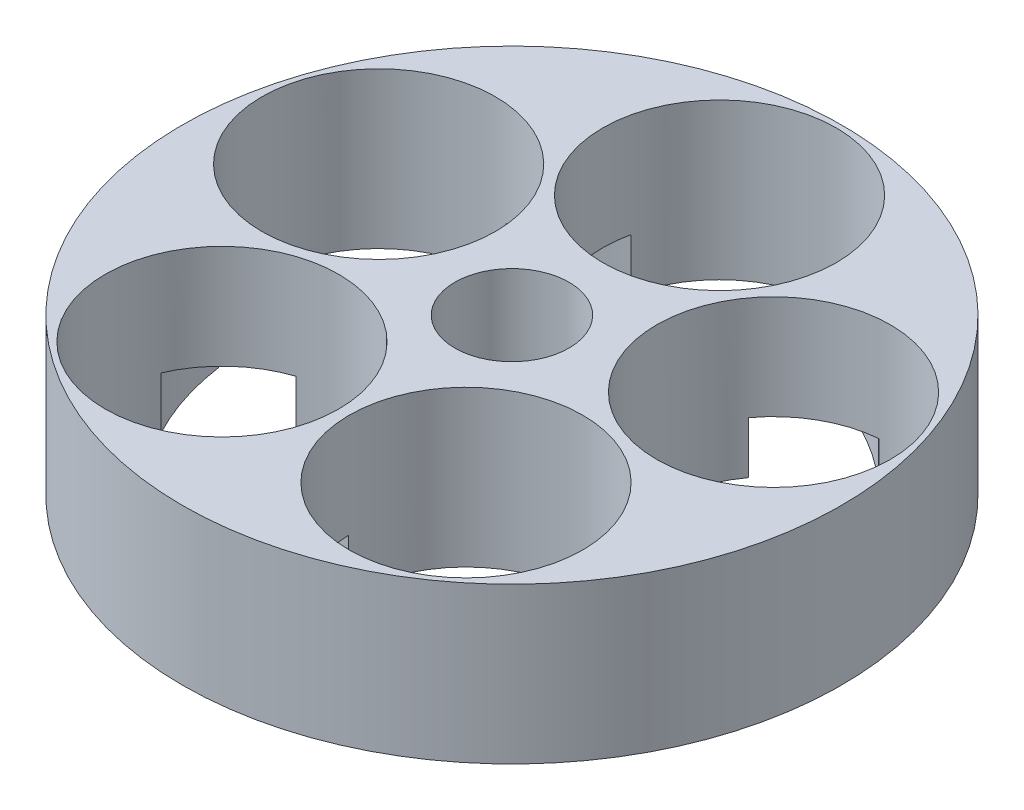
SolidWorks part; units mm, degrees
ref_plane "Front Plane" through (0, 0, 0) normal (0, 0, 1) x (1, 0, 0)
ref_plane "Top Plane" through (0, 0, 0) normal (0, 1, 0) x (1, 0, 0)
ref_plane "Right Plane" through (0, 0, 0) normal (1, 0, 0) x (0, 0, -1)
sketch "Sketch1" plane through (0, 0, 0) normal (0, 1, 0) x (1, 0, 0)
  line L0 (0, -164.5173) -> (0, 163.7587) construction
  line L1 (-104.9541, 34.1017) -> (106.3821, -34.5656) construction
  line L2 (-169.6132, -123.2312) -> (93.1873, 67.7046) construction
  line L3 (-107.5036, 0) -> (118.5963, 0) construction
  line L4 (-102.8693, -33.4243) -> (102.8693, 33.4243) construction
  line L5 (-62.7697, -86.3951) -> (62.7697, 86.3951) construction
  circle A0 centre (0, 0) radius 63.5
  circle A1 centre (38.0423, 12.3607) radius 22.5
  circle A4 centre (0, 40) radius 22.5
  circle A5 centre (-38.0423, 12.3607) radius 22.5
  circle A6 centre (-23.5114, -32.3607) radius 22.5
  circle A10 centre (23.5114, -32.3607) radius 22.5
  circle A11 centre (0, 0) radius 11
  point P15 (0, 0)
  dimension "D1" = 127
  dimension "D4" = 45
  dimension "D5" = 40
  dimension "D7" = 40
  dimension "D8" = 40
  dimension "D9" = 40
  dimension "D10" = 72
  dimension "D12" = 40
  dimension "D14" = 22
  dimension "D2" = 72
  dimension "D3" = 72
  dimension "D6" = 72
  dimension "D13" = 40
extrude "Boss-Extrude1" add sketch "Sketch1" along normal blind 30
sketch "Sketch2" plane through (0, 30, 0) normal (0, 1, 0) x (1, 0, 0)
  circle A0 centre (0, 0) radius 32.5
  circle A1 centre (0, 0) radius 50
  dimension "D1" = 65
  dimension "D2" = 100
extrude "Cut-Extrude1" cut sketch "Sketch2" against normal blind 20 from offset 20 offset against normal yes
